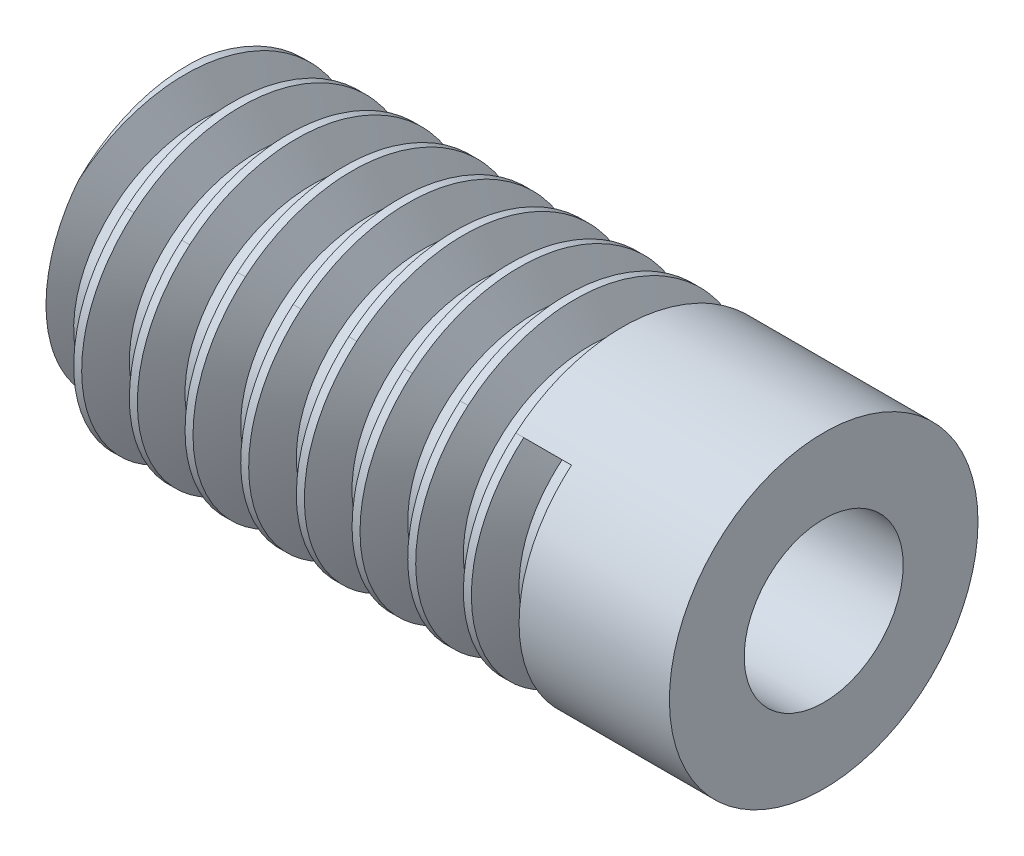
SolidWorks part; units mm, degrees
ref_plane "Front Plane" through (0, 0, 0) normal (0, 0, 1) x (1, 0, 0)
ref_plane "Top Plane" through (0, 0, 0) normal (0, 1, 0) x (1, 0, 0)
ref_plane "Right Plane" through (0, 0, 0) normal (1, 0, 0) x (0, 0, -1)
sketch "Sketch1" plane through (0, 0, 0) normal (1, 0, 0) x (0, 0, -1)
  circle A0 centre (0, 0) radius 4.85
  dimension "D1" = 9.7
extrude "Boss-Extrude1" add sketch "Sketch1" along normal blind 20
sketch "Sketch3" plane through (0, 0, 0) normal (1, 0, 0) x (0, 0, -1)
  circle A0 centre (0, 0) radius 4.85 construction
  circle A1 centre (0, 0) radius 4.85
curve "Helix/Spiral1" pitch 1.75 height 14 radius 4.85 left hand yes centre (0, 0, 0) axis (1, 0, 0) start towards (0, 0.7071, 0.7071)
sketch "Sketch6" plane through (0, 0, 0) normal (0, 0, 1) x (1, 0, 0)
  line L0 (0.2187, 4.85) -> (1.7187, 4.85)
  line L1 (20, 4.85) -> (0, 4.85) construction
  line L2 (1.7187, 4.85) -> (1.2187, 3.85)
  line L3 (1.2187, 3.85) -> (0.7187, 3.85)
  line L4 (0.7187, 3.85) -> (0.2187, 4.85)
  spline S0 degree 3 poles (0, 3.4295) (0.0362, 3.8755) (0.1095, 4.5988) (0.2187, 4.9759) (0.3281, 4.5976) (0.4375, 3.5187) (0.5469, 1.9043) (0.6562, 0) (0.7656, -1.9043) (0.875, -3.5188) (0.9844, -4.5975) (1.0937, -4.9763) (1.2031, -4.5975) (1.3125, -3.5188) (1.4583, -1.3662) (1.6042, 1.3662) (1.75, 3.5188) (1.8594, 4.5975) (1.9687, 4.9763) (2.0781, 4.5975) (2.1875, 3.5188) (2.3333, 1.3662) (2.4792, -1.3662) (2.625, -3.5188) (2.7344, -4.5975) (2.8438, -4.9763) (2.9531, -4.5975) (3.0625, -3.5188) (3.2083, -1.3662) (3.3542, 1.3662) (3.5, 3.5188) (3.6094, 4.5975) (3.7188, 4.9763) (3.8281, 4.5975) (3.9375, 3.5188) (4.0833, 1.3662) (4.2292, -1.3662) (4.375, -3.5188) (4.4844, -4.5975) (4.5938, -4.9763) (4.7031, -4.5975) (4.8125, -3.5188) (4.9583, -1.3662) (5.1042, 1.3662) (5.25, 3.5188) (5.3594, 4.5975) (5.4688, 4.9763) (5.5781, 4.5975) (5.6875, 3.5188) (5.8333, 1.3662) (5.9792, -1.3662) (6.125, -3.5188) (6.2344, -4.5975) (6.3438, -4.9763) (6.4531, -4.5975) (6.5625, -3.5188) (6.7083, -1.3662) (6.8542, 1.3662) (7, 3.5188) (7.1094, 4.5975) (7.2188, 4.9763) (7.3281, 4.5975) (7.4375, 3.5188) (7.5833, 1.3662) (7.7292, -1.3662) (7.875, -3.5188) (7.9844, -4.5975) (8.0938, -4.9763) (8.2031, -4.5975) (8.3125, -3.5188) (8.4583, -1.3662) (8.6042, 1.3662) (8.75, 3.5188) (8.8594, 4.5975) (8.9688, 4.9763) (9.0781, 4.5975) (9.1875, 3.5188) (9.3333, 1.3662) (9.4792, -1.3662) (9.625, -3.5188) (9.7344, -4.5975) (9.8438, -4.9763) (9.9531, -4.5975) (10.0625, -3.5188) (10.2083, -1.3662) (10.3542, 1.3662) (10.5, 3.5188) (10.6094, 4.5975) (10.7188, 4.9763) (10.8281, 4.5975) (10.9375, 3.5188) (11.0833, 1.3662) (11.2292, -1.3662) (11.375, -3.5188) (11.4844, -4.5975) (11.5938, -4.9763) (11.7031, -4.5975) (11.8125, -3.5188) (11.9583, -1.3662) (12.1042, 1.3662) (12.25, 3.5188) (12.3594, 4.5975) (12.4688, 4.9763) (12.5781, 4.5975) (12.6875, 3.5188) (12.8333, 1.3662) (12.9792, -1.3662) (13.125, -3.5188) (13.2344, -4.5975) (13.3438, -4.9763) (13.4531, -4.5975) (13.5625, -3.5187) (13.6719, -1.9044) (13.7813, 0.0003) (13.8905, 1.903) (13.9638, 2.9834) (14, 3.4295) knots 0 0 0 0 0.007812 0.015625 0.023437 0.03125 0.039062 0.046875 0.054687 0.0625 0.070312 0.078125 0.085937 0.09375 0.101562 0.117187 0.125 0.132812 0.140625 0.148438 0.15625 0.164062 0.179688 0.1875 0.195312 0.203125 0.210938 0.21875 0.226562 0.242188 0.25 0.257812 0.265625 0.273438 0.28125 0.289062 0.304688 0.3125 0.320312 0.328125 0.335938 0.34375 0.351562 0.367188 0.375 0.382812 0.390625 0.398438 0.40625 0.414062 0.429688 0.4375 0.445312 0.453125 0.460938 0.46875 0.476562 0.492188 0.5 0.507812 0.515625 0.523438 0.53125 0.539062 0.554688 0.5625 0.570312 0.578125 0.585938 0.59375 0.601562 0.617188 0.625 0.632812 0.640625 0.648438 0.65625 0.664062 0.679688 0.6875 0.695312 0.703125 0.710938 0.71875 0.726562 0.742188 0.75 0.757812 0.765625 0.773438 0.78125 0.789062 0.804688 0.8125 0.820312 0.828125 0.835938 0.84375 0.851562 0.867188 0.875 0.882812 0.890625 0.898438 0.90625 0.914062 0.929688 0.9375 0.945312 0.953125 0.960938 0.96875 0.976562 0.984375 0.992188 1 1 1 1 construction
  point P9 (0.9687, 3.85)
  point P11 (0.9687, 4.85)
  dimension "D1" = 1
  dimension "D2" = 1.5
  dimension "D4" = 0.5
sweep "Cut-Sweep1" cut profiles "Sketch6" path "Helix/Spiral1" align with end faces yes
sketch "Sketch12" plane through (20, 0, 0) normal (1, 0, 0) x (0, 0, -1)
  circle A0 centre (0, 0) radius 2.5
  dimension "D1" = 5
extrude "Cut-Extrude1" cut sketch "Sketch12" against normal up to next
